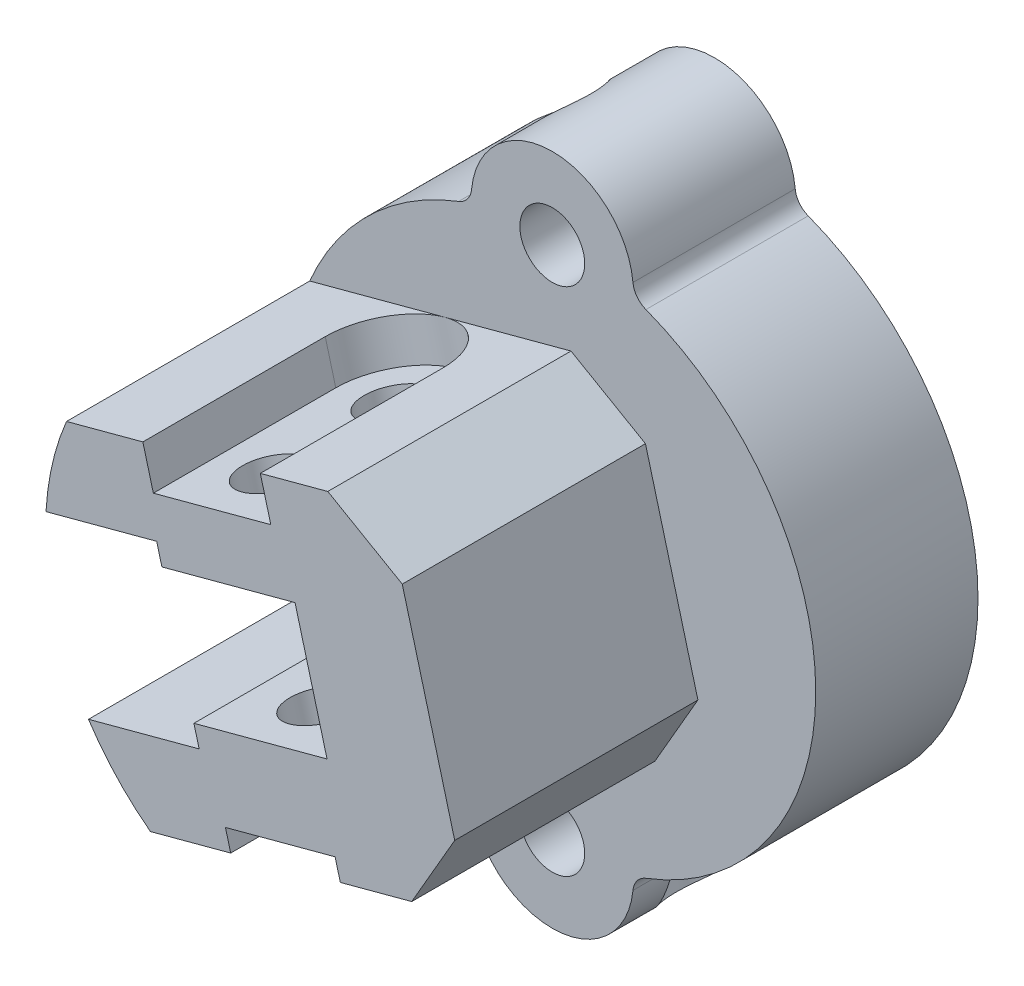
SolidWorks part; units mm, degrees
ref_plane "Front Plane" through (0, 0, 0) normal (0, 0, 1) x (1, 0, 0)
ref_plane "Top Plane" through (0, 0, 0) normal (0, 1, 0) x (1, 0, 0)
ref_plane "Right Plane" through (0, 0, 0) normal (1, 0, 0) x (0, 0, -1)
sketch "Sketch1" plane through (0, 0, 0) normal (0, 0, 1) x (1, 0, 0)
  line L0 (0, 12.6) -> (0, -12.6) construction
  line L1 (-7.5, 0) -> (7.5, 0) construction
  arc A2 (4.6209, -12.151) -> (4.6209, 12.151) centre (0, 0) ccw
  circle A4 centre (0, 12.6) radius 1.6
  circle A5 centre (0, -12.6) radius 1.6
  circle A6 centre (7.5, 0) radius 2.1 construction
  circle A7 centre (-7.5, 0) radius 2.1 construction
  arc A42 (-3.9811, -12.9886) -> (3.9811, -12.9886) centre (0, -12.6) ccw
  arc A44 (-4.6209, 12.151) -> (-4.6209, -12.151) centre (0, 0) ccw
  arc A46 (3.9811, 12.9886) -> (-3.9811, 12.9886) centre (0, 12.6) ccw
  arc A150 (-3.9811, -12.9886) -> (-4.6209, -12.151) centre (-4.9764, -13.0857) ccw
  arc A152 (-4.6209, 12.151) -> (-3.9811, 12.9886) centre (-4.9764, 13.0857) ccw
  arc A154 (3.9811, 12.9886) -> (4.6209, 12.151) centre (4.9764, 13.0857) ccw
  arc A156 (4.6209, -12.151) -> (3.9811, -12.9886) centre (4.9764, -13.0857) ccw
  point P11 (0, 0)
  dimension "D3" = 4.2
  dimension "D4" = 3.2
  dimension "D5" = 4
  dimension "D1" = 13
  dimension "D6" = 1
  dimension "D2" = 15
  dimension "D7" = 3.9811
extrude "Boss-Extrude1" add sketch "Sketch1" along normal blind 8.006
ref_axis "Axis1" through (0, 0, -0.4) along (0, 0, 1)
ref_plane "Plane2" through (0, 0, 0) normal (-0.2588, 0.9659, 0) x (0, 0, 1)
sketch "Sketch5" [suppressed] plane through (0, 0, 0) normal (0, 0, -1) x (-1, 0, 0)
  circle A2 centre (-7.5, 0) radius 2.1 construction
  circle A3 centre (7.5, 0) radius 2.1 construction
  circle A4 centre (-7.5, 0) radius 2.1
  circle A5 centre (7.5, 0) radius 2.1
extrude "Cut-Extrude3" [suppressed] cut sketch "Sketch5" against normal through all
sketch "Sketch3" plane through (0, 0, 0) normal (-0.2588, 0.9659, 0) x (0, 0, 1)
  line L0 (8.006, 13) -> (0, 13) construction
  circle A0 centre (4.003, 0) radius 2.1
  point P4 (4.003, 13)
  dimension "D1" = 4.2
extrude "Cut-Extrude1" cut sketch "Sketch3" against normal through all both and the other way through all
sketch "Sketch4" plane through (0, 0, 0) normal (0, 0, -1) x (-1, 0, 0)
  circle A0 centre (-7.5, 0) radius 3.4
  circle A1 centre (7.5, 0) radius 3.4
  dimension "D1" = 6.8
extrude "Cut-Extrude2" [suppressed] cut sketch "Sketch4" against normal blind 3 and the other way through all
sketch "Sketch6" plane through (0, 0, 8.006) normal (0, 0, 1) x (1, 0, 0)
  line L0 (-7.8272, -10.3795) -> (7.9627, -6.1486)
  line L1 (7.9627, -6.1486) -> (3.8216, 9.3062)
  line L2 (3.8216, 9.3062) -> (-11.9683, 5.0753)
  line L3 (-10.8839, -7.1092) -> (-5.4235, -5.6461)
  line L4 (-5.6823, -4.6802) -> (0.886, -2.9202)
  line L6 (-7.2611, 1.212) -> (-0.6928, 2.972)
  line L7 (0.886, -2.9202) -> (-0.6928, 2.972)
  line L8 (-5.4235, -5.6461) -> (-5.6823, -4.6802)
  line L9 (0, 0) -> (0.0966, 0.0259) construction
  line L10 (-7.5199, 2.1779) -> (-12.9803, 0.7148)
  line L11 (-7.2611, 1.212) -> (-7.5199, 2.1779)
  line L12 (0.0966, 0.0259) -> (5.8921, 1.5788) construction
  line L13 (0, 0) -> (1.1339, 0) construction
  arc A0 (-4.6209, 12.151) -> (-4.6209, -12.151) centre (0, 0) ccw construction
  arc A1 (-11.9683, 5.0753) -> (-12.9803, 0.7148) centre (0, 0) ccw
  arc A2 (-10.8839, -7.1092) -> (-7.8272, -10.3795) centre (0, 0) ccw
  point P7 (1.1339, 0)
  point P14 (0.0966, 0.0259)
  dimension "D1" = 16
  dimension "D2" = 6.1
  dimension "D3" = 6
  dimension "D4" = 0.1
  dimension "D5" = 6.8
  dimension "D6" = 1
  dimension "D7" = 15
extrude "Boss-Extrude2" add sketch "Sketch6" along normal blind 12
chamfer "Chamfer1" distance 3 angle 45 2 edges at (7.9627, -6.1486, 14.006) (3.8216, 9.3062, 14.006)
sketch "Sketch7" plane through (-2.0706, 7.7274, 0) normal (-0.2588, 0.9659, 0) x (0.9659, 0.2588, 0)
  line L0 (3.1, -20.006) -> (-10.247, -20.006) construction
  line L1 (-10.247, -20.006) -> (-10.247, -8.006) construction
  circle A0 centre (-3.347, -17.006) radius 1.55
  circle A1 centre (-3.347, -11.006) radius 1.55
  point P4 (0, 0)
  point P5 (-3.0918, -18.5034)
  point P6 (-3.0313, -17.7755)
  point P7 (-3.35, -17)
  point P9 (0, 0)
  dimension "D1" = 3.1
  dimension "D2" = 6
  dimension "D3" = 3
  dimension "D4" = 6.9
extrude "Cut-Extrude4" cut sketch "Sketch7" against normal through all and the other way through all
sketch "Sketch8" plane through (2.0706, -7.7274, 0) normal (0.2588, -0.9659, 0) x (0.9659, 0.2588, 0)
  line L0 (-6.147, 12.6226) -> (-6.147, 20.006)
  line L1 (-3.347, 14.2392) -> (-6.147, 12.6226) construction
  line L2 (-6.147, 12.6226) -> (-6.147, 9.3894)
  line L3 (-6.147, 9.3894) -> (-3.347, 7.7728)
  line L4 (-3.347, 7.7728) -> (-0.547, 9.3894)
  line L5 (-0.547, 9.3894) -> (-0.547, 12.6226)
  line L6 (-0.547, 12.6226) -> (-3.347, 14.2392) construction
  line L7 (-10.247, 20.006) -> (3.1, 20.006) construction
  line L8 (-0.547, 12.6226) -> (-0.547, 20.006)
  line L9 (-0.547, 20.006) -> (-6.147, 20.006)
  circle A0 centre (-3.347, 11.006) radius 2.8 construction
  point P1 (0, 0)
  dimension "D1" = 5.6
extrude "Cut-Extrude5" cut sketch "Sketch8" against normal blind 1 and the other way blind 2
sketch "Sketch9" plane through (-2.0706, 7.7274, 0) normal (-0.2588, 0.9659, 0) x (0.9659, 0.2588, 0)
  line L0 (-6.347, -20.006) -> (-6.347, -11.006)
  line L1 (-0.347, -11.006) -> (-0.347, -20.006)
  line L2 (-0.347, -20.006) -> (-6.347, -20.006)
  line L3 (3.1, -8.006) -> (-10.247, -8.006) construction
  line L4 (3.1, -20.006) -> (-10.247, -20.006) construction
  arc A0 (-6.347, -11.006) -> (-0.347, -11.006) centre (-3.347, -11.006) cw
  circle A1 centre (-3.347, -11.006) radius 1.55 construction
  point P4 (0, 0)
  point P10 (0, 0)
  point P11 (-0.1601, -20)
  point P14 (-7.0969, -20)
extrude "Cut-Extrude6" cut sketch "Sketch9" against normal blind 2
